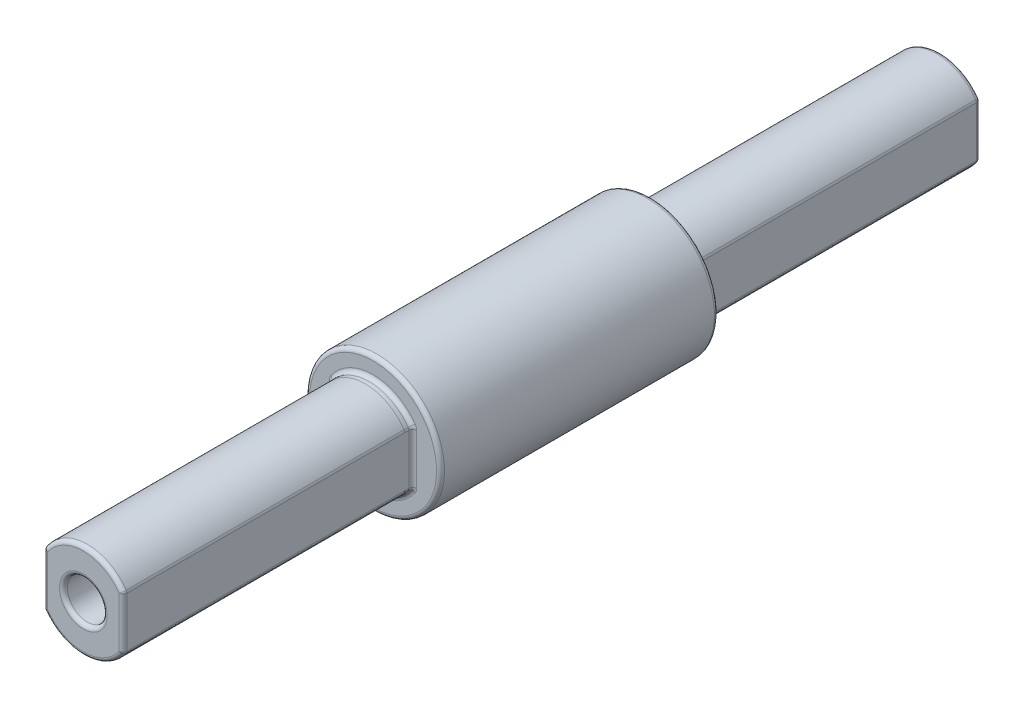
SolidWorks part; units mm, degrees
ref_plane "Alzado" through (0, 0, 0) normal (0, 0, 1) x (1, 0, 0)
ref_plane "Planta" through (0, 0, 0) normal (0, 1, 0) x (1, 0, 0)
ref_plane "Vista lateral" through (0, 0, 0) normal (1, 0, 0) x (0, 0, -1)
sketch "Croquis1" plane through (0, 0, 0) normal (1, 0, 0) x (0, 0, -1)
  line L0 (-55.0748, 0) -> (55.0748, 0) construction
  line L5 (-17.5, 8.5) -> (-17.5, 6)
  line L7 (-54, 6) -> (-54, 2.5)
  line L8 (-54, 2.5) -> (-17.5, 2.5)
  line L9 (0, 0) -> (0, 23.4689) construction
  line L12 (-17.5, 2.5) -> (0, 2.5)
  line L14 (-17.5, 8.5) -> (0, 8.5)
  line L16 (-17.5, 6) -> (-18.5, 6)
  line L17 (-18.5, 6) -> (-54, 6)
  line L18 (0, 8.5) -> (0, 2.5)
  dimension "D1" = 1
  dimension "D2" = 108
  dimension "D3" = 5
  dimension "D4" = 17
  dimension "D5" = 12
  dimension "D6" = 35
revolve "Revolución4" add sketch "Croquis1" angle 360 about L0
sketch "Croquis2" plane through (0, 0, 0) normal (1, 0, 0) x (0, 0, -1)
  line L0 (-18.5, -6) -> (-18.5, 6)
  line L2 (-54, -6) -> (-17.5, -6) construction
  point P3 (-18.5, 0)
split line "Línea de partición1"
sketch "Croquis3" plane through (0, 0, 54) normal (0, 0, 1) x (1, 0, 0)
  line L1 (-5, 3.3166) -> (5, 3.3166) construction
  line L2 (-5, 3.3166) -> (-5, -3.3166)
  line L3 (-5, -3.3166) -> (5, -3.3166) construction
  line L4 (5, 3.3166) -> (5, -3.3166)
  line L5 (-5, 3.3166) -> (5, -3.3166) construction
  line L6 (-5, -3.3166) -> (5, 3.3166) construction
  circle A0 centre (0, 0) radius 6 construction
  circle A1 centre (0, 0) radius 6 construction
  arc A2 (-5, 3.3166) -> (-5, -3.3166) centre (0, 0) ccw
  arc A3 (5, -3.3166) -> (5, 3.3166) centre (0, 0) ccw
  point P0 (0, 0)
  dimension "D1" = 10
extrude "Cortar-Extruir1" cut sketch "Croquis3" against normal up to surface (36.5 mm away) up to face at (6, 0, 17.5)
fillet "Redondeo2" radius 0.5 16 edges at (-5, 0, 17.5) (0, -6, 17.5) (-5, 3.3166, 18) (5, 3.3166, 18) (5, -3.3166, 18) (5, 0, 54) (0, -6, 54) (-5, 0, 54) (-5, 3.3166, 36.25) (5, 3.3166, 36.25) (0, 6, 54) (5, -3.3166, 36.25) (5, 0, 17.5) (0, 6, 17.5) (8.5, 0, 17.5) (2.5, 0, 54)
mirror "Simetría1" about plane through (0, 0, 0) normal (0, 0, 1) of bodies 106
